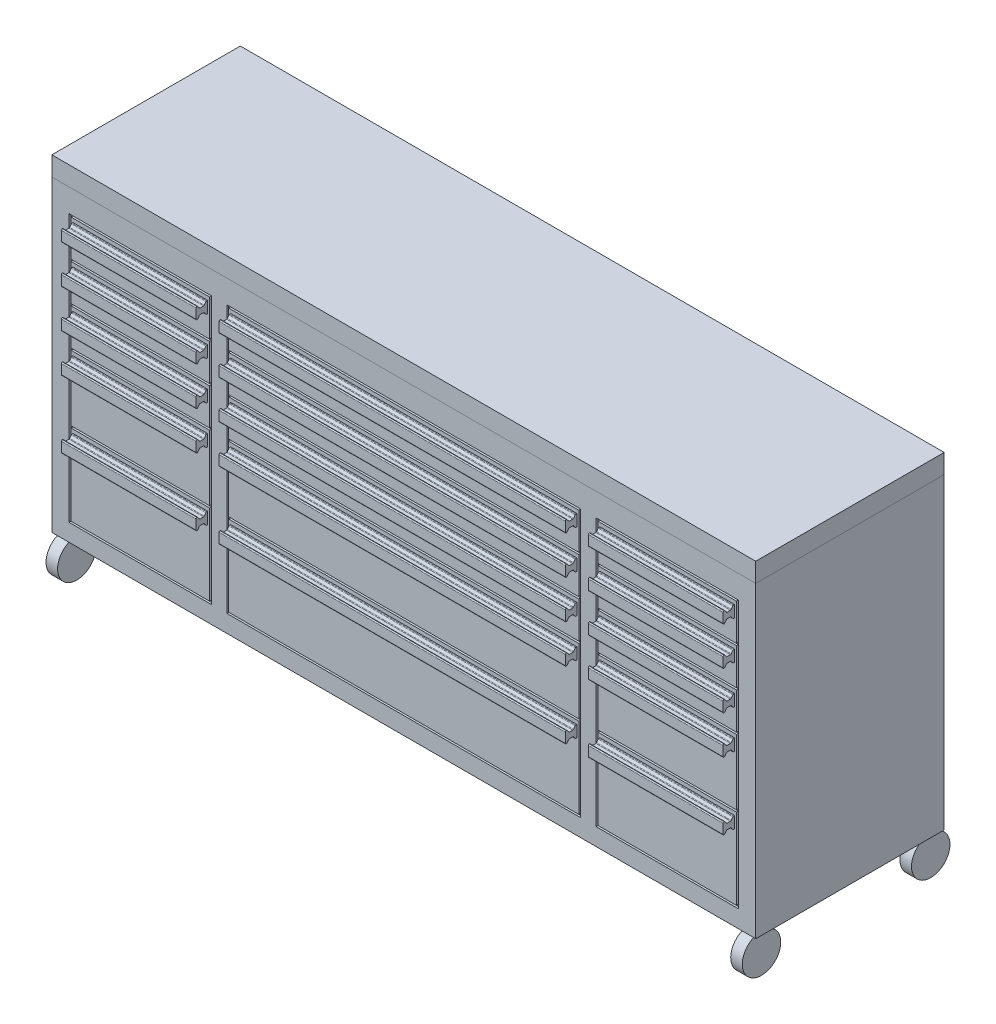
SolidWorks part; units mm, degrees
ref_plane "Front Plane" through (0, 0, 0) normal (0, 0, 1) x (1, 0, 0)
ref_plane "Top Plane" through (0, 0, 0) normal (0, 1, 0) x (1, 0, 0)
ref_plane "Right Plane" through (0, 0, 0) normal (1, 0, 0) x (0, 0, -1)
sketch "Sketch1" plane through (0, 0, 0) normal (0, 0, 1) x (1, 0, 0)
  line L1 (0, 100) -> (1830, 100)
  line L2 (0, 100) -> (0, 900)
  line L3 (0, 900) -> (1830, 900)
  line L4 (1830, 100) -> (1830, 900)
  point P4 (0, 100)
  point P6 (0, 0)
  dimension "D1" = 100
  dimension "D2" = 800
  dimension "D3" = 1830
extrude "Boss-Extrude1" add sketch "Sketch1" against normal blind 490
sketch "Sketch3" plane through (0, 900, 0) normal (0, 1, 0) x (1, 0, 0)
  line L4 (0, 0) -> (1830, 0)
  line L5 (1830, 0) -> (1830, 490)
  line L6 (1830, 490) -> (0, 490)
  line L7 (0, 490) -> (0, 0)
  line L8 (0, 0) -> (1830, 0)
  line L9 (1830, 0) -> (1830, 490)
  line L10 (1830, 490) -> (0, 490)
  line L11 (0, 490) -> (0, 0)
  dimension "D1" = 0
extrude "Boss-Extrude2" add sketch "Sketch3" along normal blind 50 separate body
sketch "Sketch4" plane through (0, 0, 0) normal (-1, 0, 0) x (0, 0, 1)
  line L0 (0, 900) -> (0, 100) construction
  line L1 (0, 825) -> (30, 825)
  line L2 (0, 825) -> (0, 795)
  line L3 (0, 795) -> (30, 795)
  line L4 (30, 825) -> (30, 795)
  line L5 (-490, 900) -> (0, 900) construction
  line L6 (3.75, 825) -> (9.375, 817.5)
  line L7 (9.375, 817.5) -> (20.625, 817.5)
  line L8 (20.625, 817.5) -> (26.25, 825)
  line L9 (0, 810) -> (30, 810) construction
  line L10 (20.625, 802.5) -> (26.25, 795)
  line L11 (9.375, 802.5) -> (20.625, 802.5)
  line L12 (3.75, 795) -> (9.375, 802.5)
  line L13 (0, 725) -> (0, 695)
  line L14 (0, 725) -> (30, 725)
  line L15 (30, 725) -> (30, 695)
  line L16 (0, 695) -> (30, 695)
  line L17 (3.75, 695) -> (9.375, 702.5)
  line L18 (9.375, 702.5) -> (20.625, 702.5)
  line L19 (20.625, 702.5) -> (26.25, 695)
  line L20 (9.375, 717.5) -> (20.625, 717.5)
  line L21 (3.75, 725) -> (9.375, 717.5)
  line L22 (20.625, 717.5) -> (26.25, 725)
  line L23 (0, 625) -> (0, 595)
  line L24 (0, 625) -> (30, 625)
  line L25 (30, 625) -> (30, 595)
  line L26 (0, 595) -> (30, 595)
  line L27 (3.75, 595) -> (9.375, 602.5)
  line L28 (9.375, 602.5) -> (20.625, 602.5)
  line L29 (20.625, 602.5) -> (26.25, 595)
  line L30 (9.375, 617.5) -> (20.625, 617.5)
  line L31 (3.75, 625) -> (9.375, 617.5)
  line L32 (20.625, 617.5) -> (26.25, 625)
  line L33 (0, 525) -> (0, 495)
  line L34 (0, 525) -> (30, 525)
  line L35 (30, 525) -> (30, 495)
  line L36 (0, 495) -> (30, 495)
  line L37 (3.75, 495) -> (9.375, 502.5)
  line L38 (9.375, 502.5) -> (20.625, 502.5)
  line L39 (20.625, 502.5) -> (26.25, 495)
  line L40 (9.375, 517.5) -> (20.625, 517.5)
  line L41 (3.75, 525) -> (9.375, 517.5)
  line L42 (20.625, 517.5) -> (26.25, 525)
  line L43 (9.375, 342.5) -> (20.625, 342.5)
  line L44 (3.75, 350) -> (9.375, 342.5)
  line L45 (20.625, 342.5) -> (26.25, 350)
  line L46 (20.625, 327.5) -> (26.25, 320)
  line L47 (9.375, 327.5) -> (20.625, 327.5)
  line L48 (0, 350) -> (0, 320)
  line L49 (0, 320) -> (30, 320)
  line L50 (30, 350) -> (30, 320)
  line L51 (0, 350) -> (30, 350)
  line L52 (3.75, 320) -> (9.375, 327.5)
  point P8 (15, 825)
  point P19 (15, 802.5)
  point P20 (15, 795)
  line M21 (0, 100) -> (0, 900)
  dimension "D1" = 30
  dimension "D3" = 30
  dimension "D2" = 75
  dimension "D4" = 15
  dimension "D5" = 22.5
  dimension "D6" = 11.25
  dimension "D8" = 70
  dimension "D10" = 145
  dimension "D7" = 4
  dimension "D9" = 2
extrude "Boss-Extrude3" add sketch "Sketch4" against normal up to surface (1830 mm away) contours L49 L52 L47 L46 L50 L51 L45 L43 L44 M21 | L42 L40 L41 L34 L36 L37 L38 L39 L35 M21 | L32 L30 L31 L24 L26 L27 L28 L29 L25 M21 | L22 L20 L21 L14 L16 L17 L18 L19 L15 M21 | L2 L9 L4 L1 L8 L7 L6 | L9 L3 L12 L11 L10 L4 M21 up to face at (1830, 500, -245)
fillet "Fillet1" radius 2.5 49 edges at (915, 320, 3.75) (915, 327.5, 9.375) (915, 320, 30) (915, 320, 26.25) (915, 327.5, 20.625) (915, 350, 30) (915, 350, 26.25) (915, 342.5, 20.625) (915, 342.5, 9.375) (915, 350, 3.75) (915, 502.5, 20.625) (915, 495, 30) (915, 495, 26.25) (915, 502.5, 9.375) (915, 495, 3.75) (915, 525, 30) (915, 525, 26.25) (915, 517.5, 20.625) (915, 517.5, 9.375) (915, 525, 3.75) (915, 602.5, 20.625) (915, 595, 30) (915, 595, 26.25) (915, 602.5, 9.375) (915, 595, 3.75) (915, 617.5, 20.625) (915, 625, 30) (915, 625, 26.25) (915, 617.5, 9.375) (915, 625, 3.75) (915, 702.5, 9.375) (915, 695, 26.25) (915, 702.5, 20.625) (915, 695, 3.75) (915, 695, 30) (915, 725, 30) (915, 725, 26.25) (915, 717.5, 9.375) (915, 725, 3.75) (915, 795, 30) (915, 795, 26.25) (915, 802.5, 20.625) (915, 802.5, 9.375) (915, 795, 3.75) (915, 825, 30) (915, 825, 26.25) (915, 817.5, 20.625) (915, 817.5, 9.375) (915, 825, 3.75)
sketch "Sketch5" plane through (0, 950, 0) normal (0, 1, 0) x (1, 0, 0)
  line L0 (1830, -30) -> (0, -30) construction
  line L1 (0, 0) -> (55, 0)
  line L2 (0, 0) -> (0, -30)
  line L3 (0, -30) -> (55, -30)
  line L4 (55, 0) -> (55, -30)
  line L5 (0, 0) -> (1830, 0) construction
  line L6 (405, 0) -> (465, 0)
  line L7 (405, 0) -> (405, -30)
  line L8 (405, -30) -> (465, -30)
  line L9 (465, 0) -> (465, -30)
  line L10 (915, 490) -> (915, 0) construction
  line L11 (1830, 490) -> (0, 490) construction
  line L12 (1425, -30) -> (1365, -30)
  line L13 (1365, 0) -> (1365, -30)
  line L14 (1425, 0) -> (1365, 0)
  line L15 (1425, 0) -> (1425, -30)
  line L16 (1830, -30) -> (1775, -30)
  line L17 (1775, 0) -> (1775, -30)
  line L18 (1830, 0) -> (1775, 0)
  line L19 (1830, 0) -> (1830, -30)
  line M11 (0, 0) -> (1830, 0)
  dimension "D1" = 55
  dimension "D2" = 60
  dimension "D3" = 350
extrude "Cut-Extrude1" cut sketch "Sketch5" against normal up to surface (850 mm away) contours L4 L2 L3 M11 | L9 L7 L8 M11 | L15 L13 L12 M11 | L19 L17 L16 M11 up to face at (915, 100, -245)
sketch "Sketch6" plane through (0, 0, 0) normal (0, 0, 1) x (1, 0, 0)
  line L0 (0, 900) -> (0, 100) construction
  line L1 (50, 835) -> (410, 835)
  line L2 (50, 835) -> (50, 740)
  line L3 (50, 150) -> (410, 150)
  line L4 (410, 835) -> (410, 740)
  line L5 (0, 100) -> (1830, 100) construction
  line L6 (0, 900) -> (1830, 900) construction
  line L7 (405, 595) -> (405, 625) construction
  line L8 (465, 595) -> (465, 625) construction
  line L9 (460, 835) -> (1370, 835)
  line L10 (460, 835) -> (460, 740)
  line L11 (460, 150) -> (1370, 150)
  line L12 (1370, 835) -> (1370, 740)
  line L13 (1365, 495) -> (1365, 525) construction
  line L14 (1830, 100) -> (1830, 900) construction
  line L15 (1780, 835) -> (1420, 835)
  line L16 (1780, 835) -> (1780, 740)
  line L17 (1780, 150) -> (1420, 150)
  line L18 (1420, 835) -> (1420, 740)
  line L19 (1425, 495) -> (1425, 525) construction
  line L20 (405, 725) -> (55, 725) construction
  line L21 (50, 740) -> (410, 740)
  line L23 (50, 735) -> (410, 735)
  line L24 (1780, 715) -> (1780, 710)
  line L26 (50, 640) -> (410, 640)
  line L27 (1780, 615) -> (1780, 610)
  line L28 (50, 635) -> (410, 635)
  line L30 (50, 540) -> (410, 540)
  line L31 (1780, 515) -> (1780, 510)
  line L32 (50, 535) -> (410, 535)
  line L34 (50, 360) -> (410, 360)
  line L35 (1780, 340) -> (1780, 335)
  line L36 (50, 365) -> (410, 365)
  line L37 (405, 350) -> (55, 350) construction
  line L38 (45, 840) -> (45, 145)
  line L39 (45, 145) -> (415, 145)
  line L40 (415, 840) -> (415, 145)
  line L41 (45, 840) -> (415, 840)
  line L42 (455, 840) -> (455, 740)
  line L43 (455, 145) -> (1375, 145)
  line L44 (1375, 840) -> (1375, 740)
  line L45 (455, 840) -> (1375, 840)
  line L46 (1785, 840) -> (1785, 740)
  line L47 (1785, 145) -> (1415, 145)
  line L48 (1415, 840) -> (1415, 740)
  line L49 (1785, 840) -> (1415, 840)
  line L50 (460, 735) -> (1370, 735)
  line L51 (460, 640) -> (1370, 640)
  line L52 (460, 635) -> (1370, 635)
  line L53 (460, 540) -> (1370, 540)
  line L54 (460, 535) -> (1370, 535)
  line L55 (460, 365) -> (1370, 365)
  line L56 (460, 360) -> (1370, 360)
  line L57 (1420, 740) -> (1780, 740)
  line L58 (1420, 735) -> (1780, 735)
  line L59 (1420, 640) -> (1780, 640)
  line L60 (1420, 635) -> (1780, 635)
  line L61 (1420, 540) -> (1780, 540)
  line L62 (1420, 535) -> (1780, 535)
  line L63 (1420, 365) -> (1780, 365)
  line L64 (1420, 360) -> (1780, 360)
  line L65 (460, 740) -> (1370, 740)
  line L66 (410, 535) -> (410, 365)
  line L67 (410, 835) -> (410, 150) construction
  line L68 (410, 735) -> (410, 640)
  line L69 (50, 735) -> (50, 640)
  line L70 (50, 835) -> (50, 150) construction
  line L71 (50, 635) -> (50, 540)
  line L72 (50, 535) -> (50, 365)
  line L73 (50, 360) -> (50, 150)
  line L74 (410, 360) -> (410, 150)
  line L75 (410, 735) -> (410, 640)
  line L76 (455, 735) -> (455, 640)
  line L77 (455, 840) -> (455, 145) construction
  line L78 (455, 635) -> (455, 540)
  line L79 (455, 535) -> (455, 365)
  line L80 (455, 360) -> (455, 145)
  line L81 (1375, 360) -> (1375, 145)
  line L82 (1375, 840) -> (1375, 145) construction
  line L83 (1375, 535) -> (1375, 365)
  line L84 (1375, 635) -> (1375, 540)
  line L85 (1375, 735) -> (1375, 640)
  line L86 (1415, 360) -> (1415, 145)
  line L87 (1415, 840) -> (1415, 145) construction
  line L88 (1415, 535) -> (1415, 365)
  line L89 (1415, 635) -> (1415, 540)
  line L90 (1415, 735) -> (1415, 640)
  line L91 (1785, 735) -> (1785, 640)
  line L92 (1785, 840) -> (1785, 145) construction
  line L93 (1785, 635) -> (1785, 540)
  line L94 (1785, 535) -> (1785, 365)
  line L95 (1785, 360) -> (1785, 145)
  line L96 (410, 635) -> (410, 540)
  line L97 (455, 540) -> (455, 535)
  line L98 (455, 635) -> (455, 640)
  line L99 (455, 735) -> (455, 740)
  line L100 (455, 365) -> (455, 360)
  line L101 (1415, 365) -> (1415, 360)
  line L102 (1375, 365) -> (1375, 360)
  line L103 (1415, 540) -> (1415, 535)
  line L104 (1375, 540) -> (1375, 535)
  line L105 (1415, 640) -> (1415, 635)
  line L106 (1375, 640) -> (1375, 635)
  line L107 (1375, 740) -> (1375, 735)
  line L108 (1415, 735) -> (1415, 740)
  line L109 (1785, 735) -> (1785, 740)
  line L110 (1785, 640) -> (1785, 635)
  line L111 (1785, 540) -> (1785, 535)
  line L112 (1785, 365) -> (1785, 360)
  line L113 (460, 735) -> (460, 640)
  line L114 (460, 835) -> (460, 150) construction
  line L115 (460, 635) -> (460, 540)
  line L116 (460, 535) -> (460, 365)
  line L117 (460, 360) -> (460, 150)
  line L118 (1370, 360) -> (1370, 150)
  line L119 (1370, 835) -> (1370, 150) construction
  line L120 (1370, 535) -> (1370, 365)
  line L121 (1370, 635) -> (1370, 540)
  line L122 (1370, 735) -> (1370, 640)
  line L123 (1420, 735) -> (1420, 640)
  line L124 (1420, 835) -> (1420, 150) construction
  line L125 (1420, 635) -> (1420, 540)
  line L126 (1420, 535) -> (1420, 365)
  line L127 (1420, 360) -> (1420, 150)
  line L128 (1780, 360) -> (1780, 150)
  line L129 (1780, 835) -> (1780, 150) construction
  line L130 (1780, 535) -> (1780, 365)
  line L131 (1780, 635) -> (1780, 540)
  line L132 (1780, 735) -> (1780, 640)
  dimension "D1" = 50
  dimension "D2" = 50
  dimension "D3" = 65
  dimension "D4" = 5
  dimension "D5" = 5
  dimension "D6" = 5
  dimension "D7" = 50
  dimension "D8" = 5
  dimension "D9" = 5
  dimension "D10" = 10
  dimension "D12" = 95
  dimension "D14" = 10
  dimension "D15" = 5
  dimension "D16" = 5
  dimension "D17" = 5
  dimension "D11" = 3
  dimension "D13" = 2
extrude "Cut-Extrude2" cut sketch "Sketch6" against normal blind 5
ref_plane "Plane1" through (0, 0, -25) normal (0, 0, 1) x (1, 0, 0)
sketch "Sketch9" plane through (0, 0, -25) normal (0, 0, 1) x (1, 0, 0)
  line L1 (10, 100) -> (40, 100)
  line L2 (10, 100) -> (10, 50)
  line L3 (10, 50) -> (40, 50)
  line L4 (40, 100) -> (40, 50)
  line L6 (0, 100) -> (1830, 100) construction
  line L7 (0, 900) -> (0, 100) construction
  point P11 (25, 100)
  dimension "D1" = 50
  dimension "D2" = 30
  dimension "D3" = 25
revolve "Revolve1" add sketch "Sketch9" angle 360 about L3
pattern_linear "LPattern3" count 2 spacing 1780 along (1, 0, 0) count 2 spacing 440 along (0, 0, -1) of bodies 127
equation "\"Length\"= 1830mm"
equation "\"Width\"= 490mm"
equation "\"Height\" = 950mm"
equation "\"Wheel Height\"= 100mm"
equation "\"Desktop Thickness\"= 50mm"
equation "\"D1@Sketch1\"=\"Wheel Height\""
equation "\"D2@Sketch1\"=\"Height\"-\"Wheel Height\"-\"Desktop Thickness\""
equation "\"D3@Sketch1\"=\"Length\""
equation "\"D1@Boss-Extrude1\"=\"Width\""
equation "\"D1@Boss-Extrude2\"=\"Desktop Thickness\""
equation "\"D4@Sketch4\"=\"D1@Sketch4\"/2"
equation "\"D5@Sketch4\"=\"D3@Sketch4\"*0.75"
equation "\"D6@Sketch4\"=\"D5@Sketch4\"*0.5"
equation "\"Small Drawer Size\"= 350mm"
equation "\"D3@Sketch5\"=\"Small Drawer Size\""
equation "\"D1@Sketch9\"=\"Wheel Height\"/2"
equation "\"D3@LPattern3\"=\"Length\"-50mm"
equation "\"D4@LPattern3\"=\"Width\"-50"
